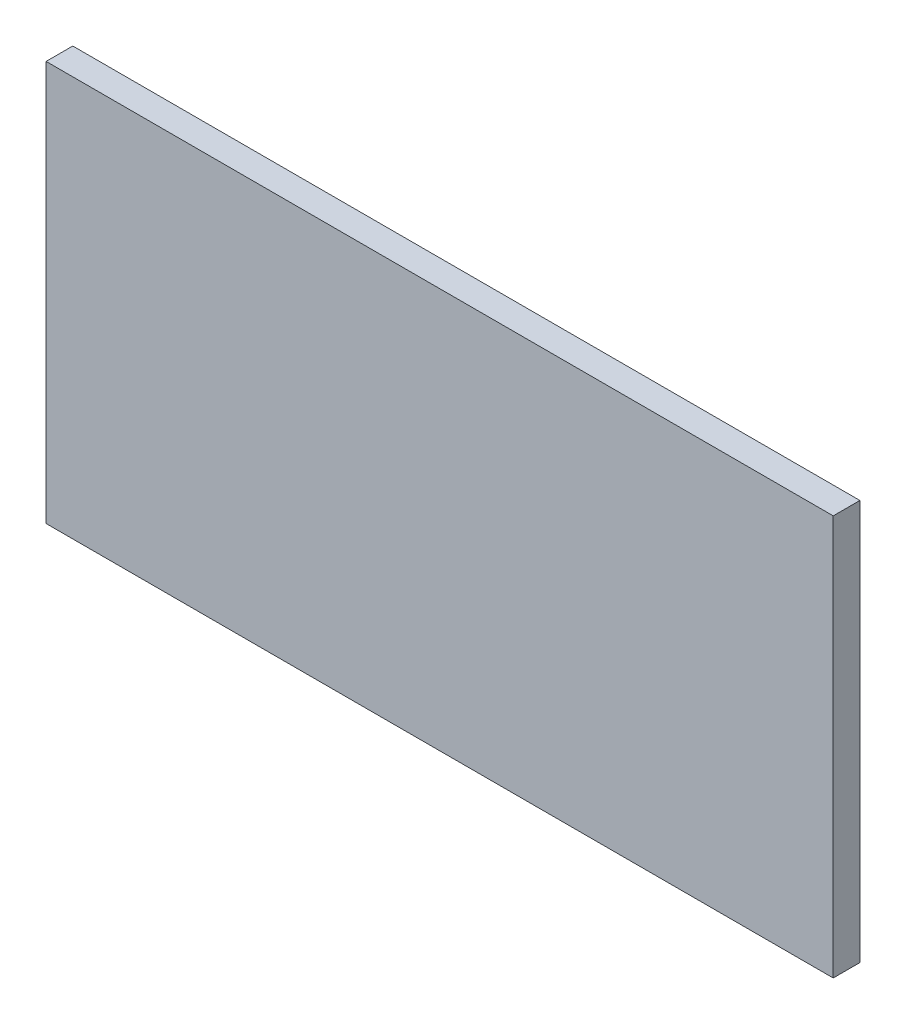
SolidWorks part; units mm, degrees
material "201 Annealed Stainless Steel (SS)"
ref_plane "Front Plane" through (0, 0, 0) normal (0, 0, 1) x (1, 0, 0)
ref_plane "Top Plane" through (0, 0, 0) normal (0, 1, 0) x (1, 0, 0)
ref_plane "Right Plane" through (0, 0, 0) normal (1, 0, 0) x (0, 0, -1)
sketch "Sketch1" plane through (0, 0, 0) normal (0, 0, 1) x (1, 0, 0)
  line L1 (-29.5, -15) -> (29.5, -15)
  line L2 (-29.5, -15) -> (-29.5, 15)
  line L3 (-29.5, 15) -> (29.5, 15)
  line L4 (29.5, -15) -> (29.5, 15)
  line L5 (-29.5, -15) -> (29.5, 15) construction
  line L6 (-29.5, 15) -> (29.5, -15) construction
  point P0 (0, 0)
  dimension "D1" = 59
  dimension "D2" = 30
extrude "Boss-Extrude1" add sketch "Sketch1" along normal blind 2
sketch "Sketch2" [suppressed] plane through (0, 0, 0) normal (0, 0, -1) x (-1, 0, 0)
  line L0 (61, 200) -> (61, -200) construction
  line L1 (-61, 314.7216) -> (-204.3993, 314.7216)
  line L2 (-61, 314.7216) -> (-61, -251.9618)
  line L3 (-61, -251.9618) -> (-204.3993, -251.9618)
  line L4 (-204.3993, 314.7216) -> (-204.3993, -251.9618)
  line L6 (61, 279.3211) -> (244.4765, 279.3211)
  line L7 (61, 279.3211) -> (61, -295.1839)
  line L8 (61, -295.1839) -> (244.4765, -295.1839)
  line L9 (244.4765, 279.3211) -> (244.4765, -295.1839)
  line L10 (-61, -200) -> (-61, -140) construction
extrude "Cut-Extrude1" [suppressed] cut sketch "Sketch2" against normal through all
sketch "Sketch3" [suppressed] plane through (49, 0, 0) normal (1, 0, 0) x (0, 0, -1)
  circle A0 centre (-6.722, 55.3681) radius 5.3835
surface "Surface-Extrude1" [suppressed] sketch "Sketch3"
sketch "Sketch4" [suppressed] plane through (-49, 0, 0) normal (-1, 0, 0) x (0, 0, 1)
  line L1 (2, 80) -> (0, 80) construction
  line L2 (0, -80) -> (0, 80) construction
  point P0 (7.5, 76)
  dimension "D1" = 4
  dimension "D2" = 7.5
ref_axis "Axis1" [suppressed] through (-49, 76, 7.5) along (1, 0, 0)
sketch "Sketch5" [suppressed] plane through (0, 0, 0) normal (0, 0, -1) x (-1, 0, 0)
  line L0 (49, 80) -> (49, -80) construction
  line L1 (-49, 80) -> (49, 80)
  line L2 (-49, 80) -> (-49, 60.2594)
  line L3 (-49, 60.2594) -> (49, 60.2594)
  line L4 (49, 80) -> (49, 60.2594)
extrude "Cut-Extrude2" [suppressed] cut sketch "Sketch5" against normal blind 3
sketch "Sketch6" [suppressed] plane through (0, 0, 2) normal (0, 0, 1) x (1, 0, 0)
  line L2 (0, -1.1) -> (0, 1.1) construction
  line L3 (-30, -15) -> (30, -15) construction
  circle A0 centre (0, -15) radius 20
  dimension "D1" = 40
extrude "Cut-Extrude3" [suppressed] cut sketch "Sketch6" against normal through all
